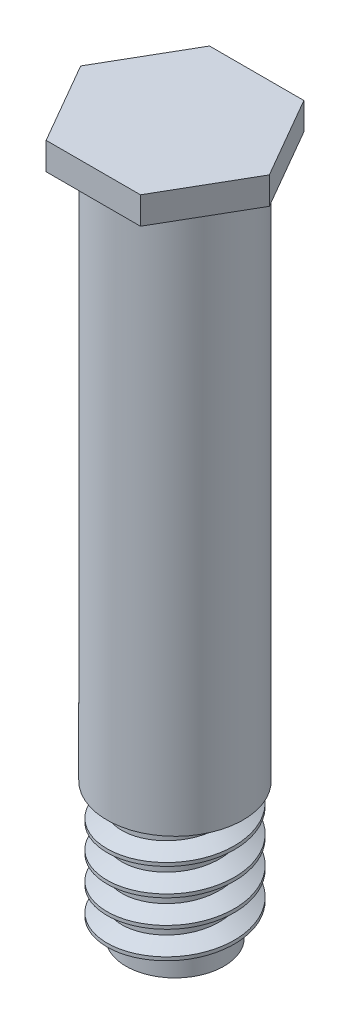
SolidWorks part; units mm, degrees
material "Alumina"
ref_plane "Front Plane" through (0, 0, 0) normal (0, 0, 1) x (1, 0, 0)
ref_plane "Top Plane" through (0, 0, 0) normal (0, 1, 0) x (1, 0, 0)
ref_plane "Right Plane" through (0, 0, 0) normal (1, 0, 0) x (0, 0, -1)
sketch "Sketch1" plane through (0, 0, 0) normal (0, 1, 0) x (1, 0, 0)
  circle A0 centre (0, 0) radius 3.175
  dimension "D1" = 6.35
extrude "Boss-Extrude1" add sketch "Sketch1" along normal blind 31.75
sketch "Sketch2" plane through (0, 31.75, 0) normal (0, 1, 0) x (1, 0, 0)
  line L1 (2.1997, -3.81) -> (4.3994, 0)
  line L2 (4.3994, 0) -> (2.1997, 3.81)
  line L3 (2.1997, 3.81) -> (-2.1997, 3.81)
  line L4 (-2.1997, 3.81) -> (-4.3994, 0)
  line L5 (-4.3994, 0) -> (-2.1997, -3.81)
  line L6 (-2.1997, -3.81) -> (2.1997, -3.81)
  circle A0 centre (0, 0) radius 3.81 construction
  dimension "D1" = 7.62
extrude "Boss-Extrude2" add sketch "Sketch2" along normal blind 1.27
sketch "Sketch6" plane through (0, 0, 0) normal (0, -1, 0) x (1, 0, 0)
  circle A0 centre (0, 0) radius 3.175
  circle A1 centre (0, 0) radius 2.286
  dimension "D1" = 6.35
  dimension "D2" = 4.572
extrude "Cut-Extrude1" cut sketch "Sketch6" against normal blind 6.35
thread "Thread3" pitch 1.27 method extrude profile "Thread Profile3" start angle 0, offset 0, length 5.334, pitch 1.27, diameter 4.572
ref_plane "Plane3" through (-2.286, 6.35, 0) normal (0, 0, 1) x (-1, 0, 0)
sketch "Thread Profile3" plane through (-2.286, 6.35, 0) normal (0, 0, 1) x (-1, 0, 0)
  line L0 (0, 0) -> (0, 1.27) construction
  line L1 (0, 0) -> (0.6874, 0.3969)
  line L2 (0.6874, 0.3969) -> (0.6874, 0.5556)
  line L3 (0.6874, 0.5556) -> (0, 0.9525)
  line L4 (0.6874, 0.4762) -> (0, 0.4762) construction
  line L11 (0, 0) -> (0, 0.9525)
  point P2 (0, 0)
  dimension "Pitch" = 1.27
  dimension "Profile_Angle" = 60
  dimension "Profile_Land" = 0.1588
  dimension "Profile_Height" = 0.6874
